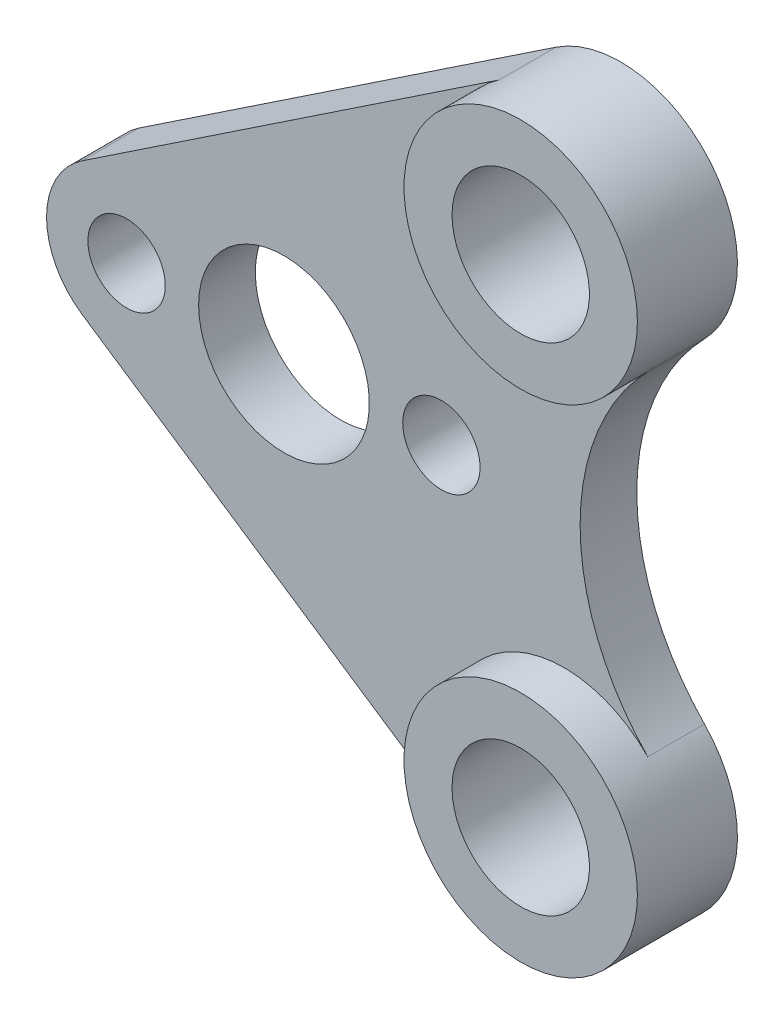
SolidWorks part; units mm, degrees
ref_plane "Front Plane" through (0, 0, 0) normal (0, 0, 1) x (1, 0, 0)
ref_plane "Top Plane" through (0, 0, 0) normal (0, 1, 0) x (1, 0, 0)
ref_plane "Right Plane" through (0, 0, 0) normal (1, 0, 0) x (0, 0, -1)
sketch "Sketch1" plane through (0, 0, 0) normal (0, 0, 1) x (1, 0, 0)
  line L0 (0, 5.1219) -> (0, -5.1219) construction
  line L1 (0, 0) -> (13.2766, 0) construction
  line L2 (8.1971, 13.145) -> (-7.6874, 2.5346)
  line L3 (-7.6874, -2.5346) -> (8.1971, -13.145)
  circle A0 centre (0, 0) radius 3.2512
  circle A1 centre (-5.9944, 0) radius 1.4732
  circle A2 centre (5.9944, 0) radius 1.4732
  circle A3 centre (10.6661, 9.4488) radius 2.6162
  circle A4 centre (10.6661, -9.4488) radius 2.6162
  arc A5 (-7.6874, 2.5346) -> (-7.6874, -2.5346) centre (-5.9944, 0) ccw
  arc A6 (8.1971, -13.145) -> (13.8546, -6.3518) centre (10.6661, -9.4488) ccw
  arc A7 (13.8546, 6.3518) -> (8.1971, 13.145) centre (10.6661, 9.4488) ccw
  arc A8 (13.8546, 6.3518) -> (13.8546, -6.3518) centre (20.3941, 0) ccw
  point P9 (0, 0)
  point P24 (0, 0)
  dimension "D1" = 2.9464
  dimension "D2" = 6.5024
  dimension "D3" = 9.0424
  dimension "D4" = 5.2324
  dimension "D5" = 18.8976
  dimension "D6" = 8.382
  dimension "D7" = 4.445
  dimension "D8" = 3.048
  dimension "D9" = 3.81
extrude "Boss-Extrude1" add sketch "Sketch1" along normal blind 3.81
sketch "Sketch2" plane through (0, 0, 3.81) normal (0, 0, 1) x (1, 0, 0)
  line L2 (8.1971, 13.145) -> (-7.6874, 2.5346)
  line L3 (-7.6874, -2.5346) -> (8.1971, -13.145)
  line L4 (8.1971, 13.145) -> (-7.6874, 2.5346)
  line L5 (-7.6874, -2.5346) -> (8.1971, -13.145)
  arc A0 (8.1971, 13.145) -> (13.8546, 6.3518) centre (10.6661, 9.4488) ccw
  arc A1 (13.8546, -6.3518) -> (8.1971, -13.145) centre (10.6661, -9.4488) ccw
  arc A4 (13.8546, 6.3518) -> (8.1971, 13.145) centre (10.6661, 9.4488) ccw
  arc A5 (-7.6874, 2.5346) -> (-7.6874, -2.5346) centre (-5.9944, 0) ccw
  arc A6 (8.1971, -13.145) -> (13.8546, -6.3518) centre (10.6661, -9.4488) ccw
  arc A7 (13.8546, 6.3518) -> (13.8546, -6.3518) centre (20.3941, 0) ccw
  arc A9 (-7.6874, 2.5346) -> (-7.6874, -2.5346) centre (-5.9944, 0) ccw
  arc A11 (13.8546, 6.3518) -> (13.8546, -6.3518) centre (20.3941, 0) ccw
  dimension "D1" = 0
extrude "Cut-Extrude2" cut sketch "Sketch2" against normal offset from surface (1.651 mm away) 2.159 up to face at (5.1514, 0, 0)
